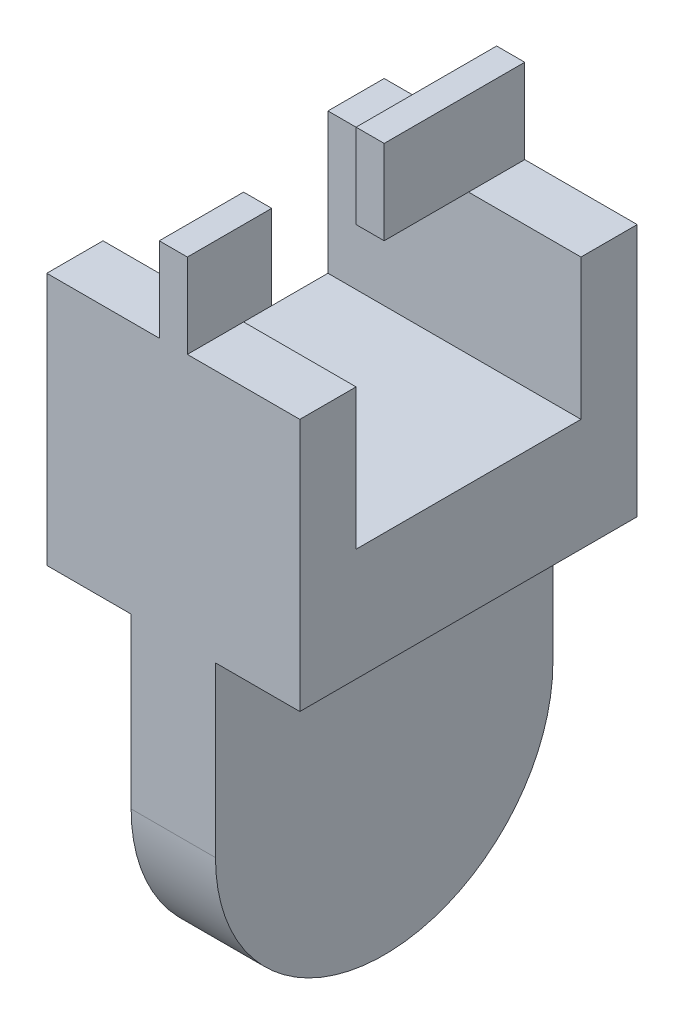
SolidWorks part; units mm, degrees
ref_plane "Front Plane" through (0, 0, 0) normal (1, 0, 0) x (0, 1, 0)
ref_plane "Top Plane" through (0, 0, 0) normal (0, 0, 1) x (0, 1, 0)
ref_plane "Right Plane" through (0, 0, 0) normal (0, 1, 0) x (-1, 0, 0)
sketch "Sketch1" plane through (0, 0, 0) normal (1, 0, 0) x (0, 1, 0)
  line L0 (0, 150) -> (450, 150)
  line L1 (450, 150) -> (450, 75)
  line L2 (450, 75) -> (375, 75)
  line L3 (375, 75) -> (375, 100)
  line L4 (375, 100) -> (250, 100)
  line L5 (250, 100) -> (250, -100)
  line L6 (250, -100) -> (375, -100)
  line L7 (375, -100) -> (375, -25)
  line L8 (375, -25) -> (450, -25)
  line L9 (450, -25) -> (450, -150)
  line L10 (450, -150) -> (0, -150)
  line L11 (150, 150) -> (150, -150)
  arc A0 (0, 150) -> (0, -150) centre (0, 0) ccw
  circle A1 centre (0, 0) radius 50
  dimension "D1" = 100
  dimension "D2" = 150
  dimension "D3" = 75
  dimension "D4" = 250
  dimension "D5" = 375
  dimension "D6" = 450
  dimension "D7" = 50
  dimension "D8" = 50
  dimension "D9" = 125
  dimension "D10" = 300
  dimension "D11" = 150
extrude "Boss-Extrude1" add sketch "Sketch1" along normal blind 112.5 contours L10 A0 L0 L1 L2 L3 L4 L5 L6 L7 L8 L9
mirror "Mirror1" about plane through (0, 0, 0) normal (1, 0, 0) of bodies 101
sketch "Sketch2" plane through (0, 0, 150) normal (0, 0, 1) x (1, 0, 0)
  line L0 (37.5, -150) -> (37.5, 150)
  line L1 (-112.5, -150) -> (112.5, -150) construction
  line L2 (37.5, 150) -> (112.5, 150)
  line L3 (112.5, 450) -> (112.5, 0) construction
  line L4 (12.5, 450) -> (12.5, 375)
  line L5 (112.5, 450) -> (-112.5, 450) construction
  line L6 (12.5, 375) -> (112.5, 375)
  line L9 (37.5, -150) -> (112.5, -150)
  line L10 (112.5, -150) -> (112.5, 150)
  line L11 (12.5, 450) -> (112.5, 450)
  line L12 (112.5, 450) -> (112.5, 375)
  line L13 (37.5, -150) -> (-37.5, -150)
  line L14 (-112.5, -150) -> (112.5, -150) construction
  line L15 (-37.5, -150) -> (-112.5, -150)
  line L16 (-112.5, -150) -> (-112.5, 150)
  line L17 (-112.5, 450) -> (-112.5, 0) construction
  line L18 (-112.5, 150) -> (-37.5, 150)
  line L19 (-37.5, 150) -> (-37.5, -150)
  line L20 (-12.5, 375) -> (-112.5, 375)
  line L21 (-112.5, 375) -> (-112.5, 450)
  line L22 (-112.5, 450) -> (-12.5, 450)
  line L23 (112.5, 450) -> (-112.5, 450) construction
  line L24 (-12.5, 450) -> (-12.5, 375)
  line L25 (112.5, 0) -> (-112.5, 0) construction
  point P27 (0, 0)
  dimension "D1" = 100
  dimension "D2" = 125
  dimension "D3" = 300
  dimension "D4" = 150
  dimension "D5" = 75
  dimension "D6" = 375
extrude "Cut-Extrude2" cut sketch "Sketch2" against normal through all contours L10 L2 L0 L9 | L15 L16 L18 L19 | L24 L20 L21 L22 | L12 L6 L4 L11
